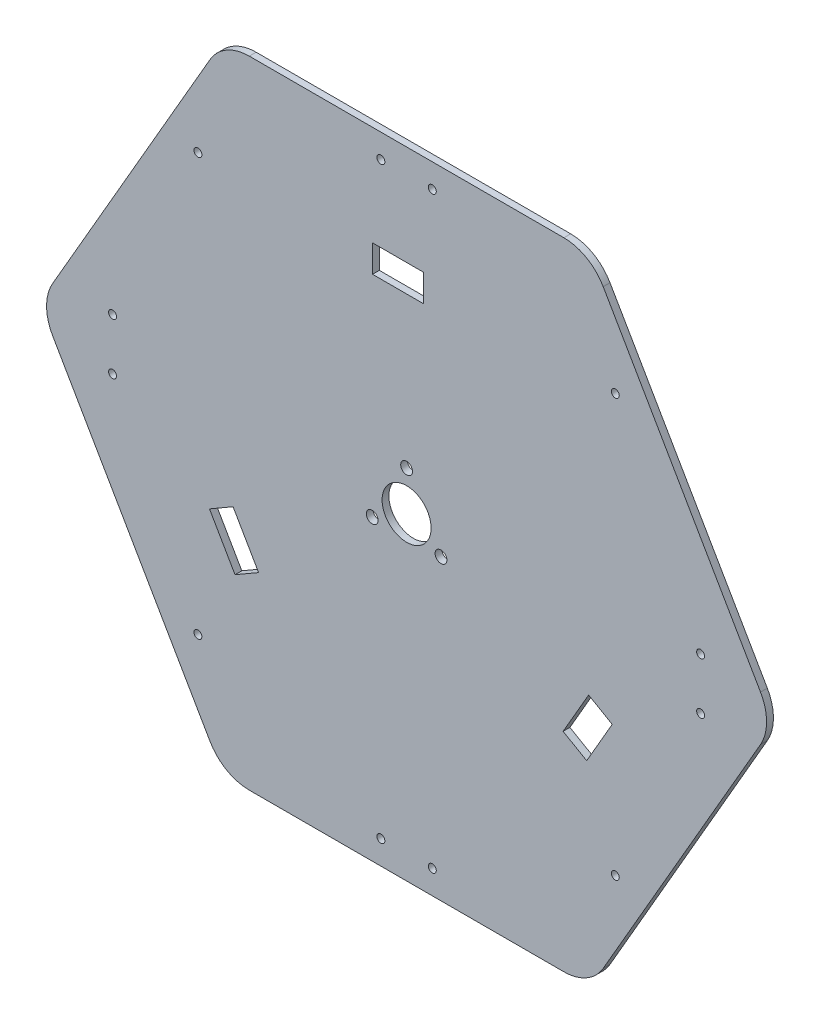
SolidWorks part; units mm, degrees
ref_plane "Alzado" through (0, 0, 0) normal (0, 0, 1) x (1, 0, 0)
ref_plane "Planta" through (0, 0, 0) normal (0, 1, 0) x (1, 0, 0)
ref_plane "Vista lateral" through (0, 0, 0) normal (1, 0, 0) x (0, 0, -1)
sketch "Croquis1" plane through (0, 0, 0) normal (0, 0, 1) x (1, 0, 0)
  line L0 (7.5, 95.9218) -> (-15, 83.9218) construction
  line L1 (-15, 95.9218) -> (7.5, 95.9218)
  line L2 (-15, 95.9218) -> (-15, 83.9218)
  line L3 (-15, 83.9218) -> (7.5, 83.9218)
  line L4 (7.5, 95.9218) -> (7.5, 83.9218)
  line L5 (-15, 95.9218) -> (7.5, 83.9218) construction
  line L6 (90.5708, -34.9705) -> (80.1784, -28.9705)
  line L7 (90.5708, -34.9705) -> (79.3208, -54.4561)
  line L8 (79.3208, -54.4561) -> (68.9284, -48.4561)
  line L9 (80.1784, -28.9705) -> (68.9284, -48.4561)
  line L10 (-75.5708, -60.9513) -> (-65.1784, -54.9513)
  line L11 (-75.5708, -60.9513) -> (-86.8208, -41.4657)
  line L12 (-86.8208, -41.4657) -> (-76.4284, -35.4657)
  line L13 (-65.1784, -54.9513) -> (-76.4284, -35.4657)
  line L14 (0, -0.7536) -> (0, 0) construction
  line L15 (0, 0) -> (0, 17.5) construction
  line L17 (-80.829, -140) -> (80.829, -140)
  line L18 (80.829, -140) -> (161.6581, 0)
  line L19 (161.6581, 0) -> (80.829, 140)
  line L20 (80.829, 140) -> (-80.829, 140)
  line L21 (-80.829, 140) -> (-161.6581, 0)
  line L22 (-161.6581, 0) -> (-80.829, -140)
  circle A0 centre (0, 0) radius 150
  circle A1 centre (0, 0) radius 10.8
  circle A2 centre (0, 0) radius 90 construction
  circle A3 centre (-3.75, 89.9218) radius 40 construction
  circle A4 centre (79.7496, -41.7133) radius 40 construction
  circle A5 centre (-75.9996, -48.2085) radius 40 construction
  circle A6 centre (0, 0) radius 17.5 construction
  circle A7 centre (0, 17.5) radius 2.6
  circle A8 centre (0, 0) radius 140 construction
  circle A9 centre (15.1554, -8.75) radius 2.6
  circle A10 centre (-15.1554, -8.75) radius 2.6
  point P11 (-3.75, 89.9218)
  point P18 (0, 0)
  point P28 (0, 0)
  point P29 (0, 90)
  point P39 (0, 0)
  point P43 (0, 90)
  point P44 (0, 90)
  point P45 (-3.9078, 89.9151)
  point P46 (0, 140)
  dimension "D1" = 300
  dimension "D2" = 21.6
  dimension "D3" = 180
  dimension "D4" = 80
  dimension "D9" = 5.2
  dimension "D10" = 3
  dimension "D11" = 50
  dimension "D5" = 12
  dimension "D6" = 22.5
  dimension "D12" = 3.75
  dimension "D7" = 3
  dimension "D8" = 3
extrude "Saliente-Extruir1" add sketch "Croquis1" along normal blind 3 contours L19 A0 L20 L21 L22 L17 L18 A10 A9 A7 A1 L1 L4 L3 L2 L9 L6 L7 L8 L13 L10 L11 L12 | A0 L20 L21 | A0 L19 L20 | A0 L18 L19 | A0 L17 L18 | A0 L22 L17 | A0 L21 L22 region at (-76.7492, -132.9335, 0) region at (-72.9482, -126.3499, 0) region at (76.7492, -132.9335, 0) region at (-153.4984, 0, 0) region at (153.4984, 0, 0) region at (-76.7492, 132.9335, 0) region at (76.7492, 132.9335, 0)
fillet "Redondeo1" radius 20 6 edges at (80.829, 140, 1.5) (-80.829, 140, 1.5) (-161.6581, 0, 1.5) (-80.829, -140, 1.5) (80.829, -140, 1.5) (161.6581, 0, 1.5)
sketch "Croquis2" plane through (0, 0, 0) normal (0, 0, -1) x (-1, 0, 0)
  circle A0 centre (0, 0) radius 102.5 construction
  circle A1 centre (0, 0) radius 140 construction
  dimension "D1" = 280
  dimension "D2" = 205
sketch "Croquis3" plane through (0, 0, 0) normal (0, 0, -1) x (1, 0, 0)
  circle A0 centre (129.5053, 11.3302) radius 1.75
  circle A1 centre (91.9239, 91.9239) radius 1.75
  circle A2 centre (11.3302, 129.5053) radius 1.75
extrude "Cortar-Extruir1" cut sketch "Croquis3" against normal through all
pattern_circular "MatrizC1" count 4 over 360 about axis through (0, 0, 0) along (0, 0, 1) of "Cortar-Extruir1"
